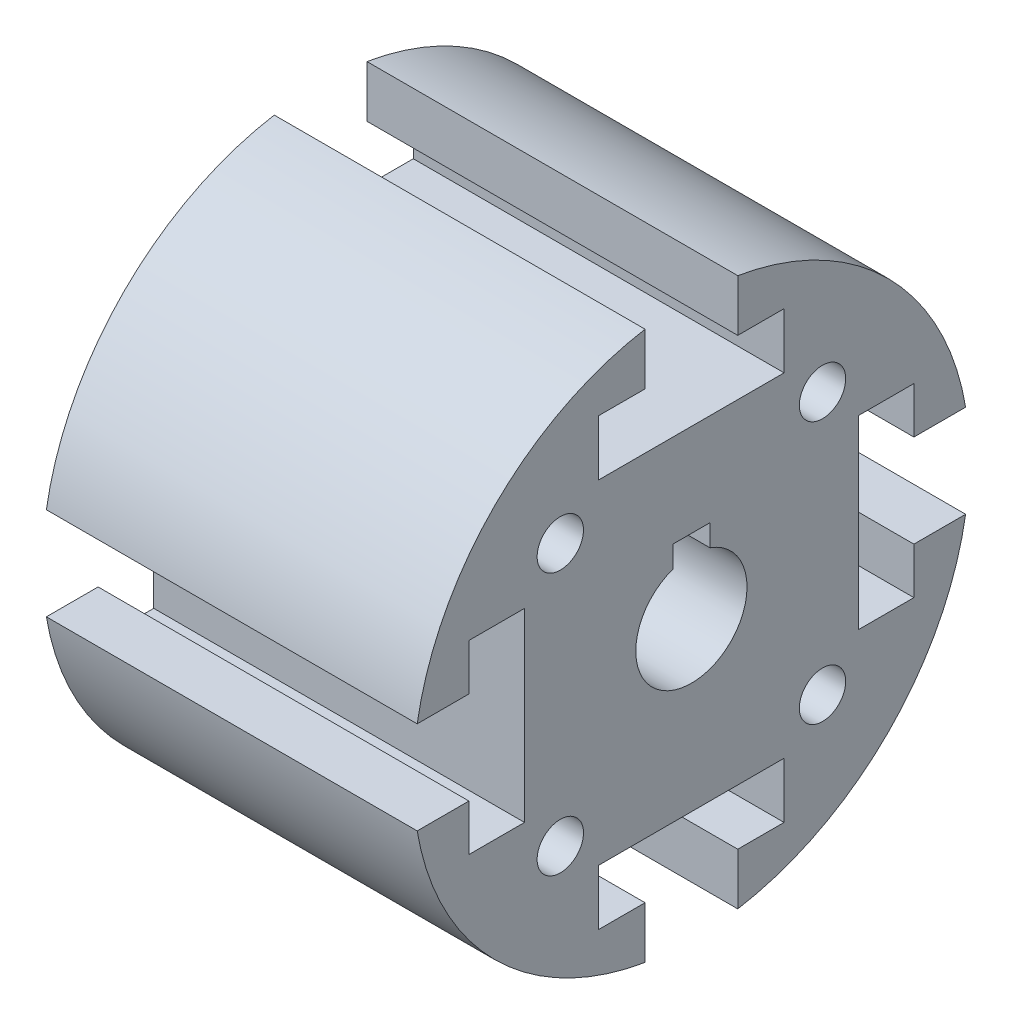
SolidWorks part; units mm, degrees
ref_plane "正面" through (0, 0, 0) normal (0, 0, 1) x (1, 0, 0)
ref_plane "平面" through (0, 0, 0) normal (0, 1, 0) x (1, 0, 0)
ref_plane "右側面" through (0, 0, 0) normal (1, 0, 0) x (0, 0, -1)
ref_plane "平面1" through (0, 0, 0) normal (0, 0.7071, -0.7071) x (-1, 0, 0)
ref_plane "平面2" through (0, 0, 0) normal (0, -0.7071, -0.7071) x (-1, 0, 0)
sketch "ｽｹｯﾁ1" plane through (0, 0, 0) normal (1, 0, 0) x (0, 0, -1)
  circle A0 centre (0, 0) radius 15
  dimension "D1" = 30
extrude "ﾎﾞｽ - 押し出し1" add sketch "ｽｹｯﾁ1" along normal blind 10 and the other way blind 10
sketch "ｽｹｯﾁ2" plane through (10, 0, 0) normal (1, 0, 0) x (0, 0, -1)
  circle A1 centre (0, 0) radius 3
  dimension "D1" = 6
extrude "ｶｯﾄ - 押し出し1" cut sketch "ｽｹｯﾁ2" against normal through all
sketch "ｽｹｯﾁ3" plane through (10, 0, 0) normal (1, 0, 0) x (0, 0, -1)
  line L0 (5, 12) -> (2.5, 12)
  line L1 (-5, 9) -> (5, 9)
  line L2 (-5, 9) -> (-5, 12)
  line L4 (5, 9) -> (5, 12)
  line L6 (-2.5, 15) -> (-2.5, 12)
  line L7 (-2.5, 12) -> (-5, 12)
  line L8 (2.5, 15) -> (2.5, 12)
  line L9 (-2.5, 15) -> (2.5, 15)
  circle A1 centre (0, 0) radius 15 construction
  point P2 (0, 9)
  point P4 (0, 15)
  dimension "D1" = 10
  dimension "D2" = 6
  dimension "D3" = 3
  dimension "D4" = 5
extrude "ｶｯﾄ - 押し出し2" cut sketch "ｽｹｯﾁ3" against normal through all
sketch "ｽｹｯﾁ4" plane through (10, 0, 0) normal (1, 0, 0) x (0, 0, -1)
  line L0 (-7.0711, 7.0711) -> (7.0711, 7.0711) construction
  line L1 (7.0711, 7.0711) -> (7.0711, -7.0711) construction
  line L2 (7.0711, -7.0711) -> (-7.0711, -7.0711) construction
  line L3 (-7.0711, -7.0711) -> (-7.0711, 7.0711) construction
  line L4 (-7.0711, 7.0711) -> (7.0711, -7.0711) construction
  line L5 (7.0711, 7.0711) -> (-7.0711, -7.0711) construction
  circle A0 centre (7.0711, 7.0711) radius 4
  circle A1 centre (7.0711, -7.0711) radius 4
  circle A2 centre (-7.0711, -7.0711) radius 4
  circle A3 centre (-7.0711, 7.0711) radius 4
  point P2 (0, 0)
  dimension "D2" = 8
  dimension "D1" = 20
hole_wizard "M3x0.5 ねじ穴1" positions "ｽｹｯﾁ5" profile "ｽｹｯﾁ6" tap size "M3x0.5" standard "JIS" end condition through all
sketch "ｽｹｯﾁ5" plane through (10, 0, 0) normal (1, 0, 0) x (0, 0, -1)
  point P15 (-7.0711, 7.0711)
  point P18 (7.0711, -7.0711)
  point P21 (7.0711, 7.0711)
  point P24 (-7.0711, -7.0711)
sketch "ｽｹｯﾁ6" plane through (10, 7.0711, 7.0711) normal (0, 1, 0) x (0, 0, -1)
  line L0 (0, 0) -> (0, 20)
  line L1 (0, 20) -> (1.25, 20)
  line L2 (1.25, 20) -> (1.25, 0)
  line L5 (1.25, 0) -> (0, 0)
  line L11 (0, -6.35) -> (0, 107.95) construction
  dimension "ねじ山の主要直径" = 2.5
  dimension "次ｻｰﾌｪｽまでのねじ下穴ﾄﾞﾘﾙの深さ" = 20
pattern_circular "円形ﾊﾟﾀｰﾝ2" count 4 over 360 about axis through (-10, 0, 0) along (1, 0, 0) of "ｶｯﾄ - 押し出し2"
sketch "ｽｹｯﾁ7" plane through (10, 0, 0) normal (1, 0, 0) x (0, 0, -1)
  line L0 (-1, 3) -> (1, 3) construction
  line L1 (-1, 4) -> (1, 4)
  line L2 (-1, 4) -> (-1, 3)
  line L4 (1, 4) -> (1, 3)
  line L5 (-1, 3) -> (-1, 2.8284)
  line L6 (1, 3) -> (1, 2.8284)
  arc A0 (1, 2.8284) -> (-1, 2.8284) centre (0, 0) ccw
  circle A2 centre (0, 0) radius 3 construction
  point P4 (0, 3)
  dimension "D1" = 2
  dimension "D2" = 1
extrude "ｶｯﾄ - 押し出し3" cut sketch "ｽｹｯﾁ7" against normal through all
